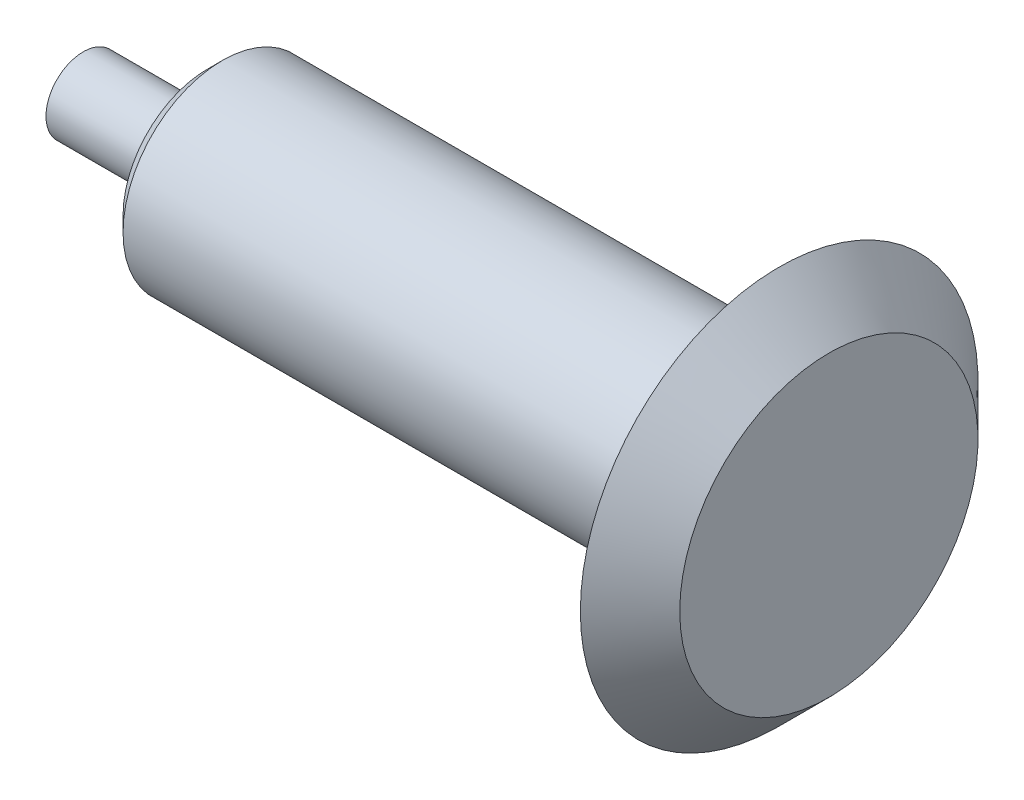
SolidWorks part; units mm, degrees
ref_plane "前基準面" through (0, 0, 0) normal (0, 0, 1) x (1, 0, 0)
ref_plane "上基準面" through (0, 0, 0) normal (0, 1, 0) x (1, 0, 0)
ref_plane "右基準面" through (0, 0, 0) normal (1, 0, 0) x (0, 0, -1)
ref_plane "平面1"
sketch "草圖1" plane through (0, 0, 0) normal (0, 0, 1) x (1, 0, 0)
  line L0 (0, 0) -> (25, 0)
  line L1 (25, 0) -> (25, 7.5)
  line L2 (25, 7.5) -> (0, 7.5)
  line L3 (0, 7.5) -> (0, 0)
  line L4 (25, 0) -> (140, 0) construction
  line L5 (140, 0) -> (150, 0)
  line L6 (150, 0) -> (150, 40)
  line L7 (150, 40) -> (140, 40)
  line L8 (140, 40) -> (140, 0)
  line L9 (140, 20) -> (25, 20)
  line L10 (25, 20) -> (25, 0)
  line L11 (25, 0) -> (140, 0)
  line L12 (140, 0) -> (140, 20)
  dimension "D1" = 25
  dimension "D2" = 7.5
  dimension "D3" = 115
  dimension "D4" = 20
  dimension "D5" = 10
  dimension "D6" = 40
revolve "迴轉1" add sketch "草圖1" angle 360 about L4 region at (12.5, 3.75, 0) region at (82.5, 10, 0) region at (145, 20, 0)
chamfer "倒角1" distance 10 distance2 10 1 edges at (150, 0, 40)
chamfer "倒角2" distance 10 distance2 10 1 edges at (140, 0, 20)
chamfer "倒角3" distance 3 distance2 3 1 edges at (25, 0, 20)
